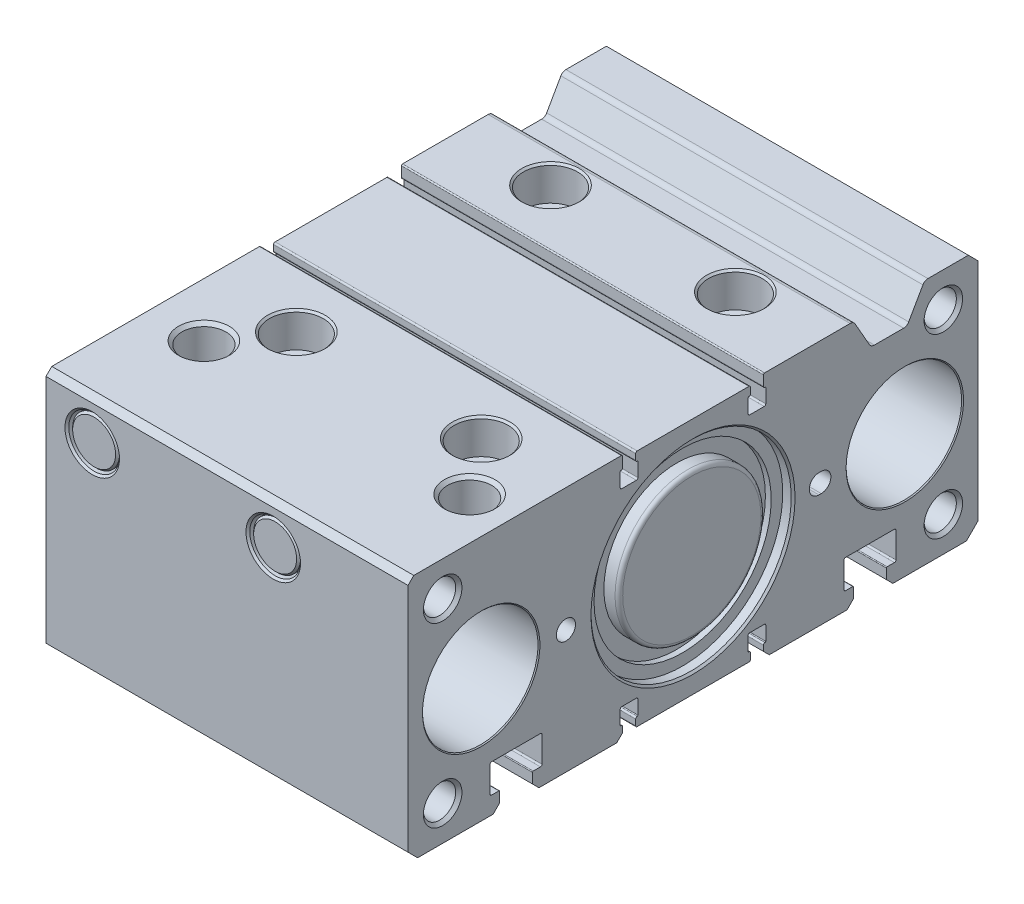
SolidWorks part; units mm, degrees
ref_plane "前视基准面" through (0, 0, 0) normal (0, 0, 1) x (1, 0, 0)
ref_plane "上视基准面" through (0, 0, 0) normal (0, 1, 0) x (1, 0, 0)
ref_plane "右视基准面" through (0, 0, 0) normal (1, 0, 0) x (0, 0, -1)
sketch "草图1" plane through (0, 0, 0) normal (1, 0, 0) x (0, 0, -1)
  line L0 (-74, 30.5) -> (-74, -29.5)
  line L1 (-74, -29.5) -> (-71.5, -32)
  line L2 (-71.5, -32) -> (-51.9, -32)
  line L3 (-51.9, -32) -> (-50.2, -30.3)
  line L4 (-50.2, -30.3) -> (-50.2, -27.7)
  line L5 (-50.4, -27.5) -> (-52.3, -27.5)
  line L6 (-52.7, -27.1) -> (-52.7, -20.4)
  line L7 (-52.3, -20) -> (-39.6, -20)
  line L8 (-39.2, -20.4) -> (-39.2, -27.1)
  line L9 (-39.6, -27.5) -> (-41.5, -27.5)
  line L10 (-41.7, -27.7) -> (-41.7, -30.3)
  line L11 (-41.7, -30.3) -> (-40, -32)
  line L12 (-40, -32) -> (-19.8, -32)
  line L13 (-19.8, -32) -> (-18.3, -30.5)
  line L14 (-18.3, -30.5) -> (-18.3, -29.1)
  line L15 (-18.9, -28.5) -> (-18.9, -24.9)
  line L16 (-18.5, -24.5) -> (-14.7, -24.5)
  line L17 (-14.3, -24.9) -> (-14.3, -28.5)
  line L18 (-14.9, -29.1) -> (-14.9, -30.6)
  line L19 (-14.5, -31) -> (14.5, -31)
  line L20 (14.9, -30.6) -> (14.9, -29.1)
  line L21 (14.3, -28.5) -> (14.3, -24.9)
  line L22 (14.7, -24.5) -> (18.5, -24.5)
  line L23 (18.9, -24.9) -> (18.9, -28.5)
  line L24 (18.3, -29.1) -> (18.3, -30.5)
  line L25 (18.3, -30.5) -> (19.8, -32)
  line L26 (19.8, -32) -> (40, -32)
  line L27 (40, -32) -> (41.7, -30.3)
  line L28 (41.7, -30.3) -> (41.7, -27.7)
  line L29 (41.5, -27.5) -> (39.6, -27.5)
  line L30 (39.2, -27.1) -> (39.2, -20.4)
  line L31 (39.6, -20) -> (52.3, -20)
  line L32 (52.7, -20.4) -> (52.7, -27.1)
  line L33 (52.3, -27.5) -> (50.4, -27.5)
  line L34 (50.2, -27.7) -> (50.2, -30.3)
  line L35 (50.2, -30.3) -> (51.9, -32)
  line L36 (51.9, -32) -> (71, -32)
  line L37 (71, -32) -> (74, -29)
  line L38 (74, -29) -> (74, 29.5)
  line L39 (74, 29.5) -> (71.5, 32)
  line L40 (71.5, 32) -> (61, 32)
  line L41 (59.6966, 31.2423) -> (56.0034, 24.7577)
  line L42 (54.7, 24) -> (47.1, 24)
  line L43 (45.7966, 24.7577) -> (42.1034, 31.2423)
  line L44 (40.8, 32) -> (18.6, 32)
  line L45 (18.3, 31.7) -> (18.3, 29.1)
  line L46 (18.9, 28.5) -> (18.9, 24.9)
  line L47 (18.5, 24.5) -> (14.7, 24.5)
  line L48 (14.3, 24.9) -> (14.3, 28.5)
  line L49 (14.9, 29.1) -> (14.9, 30.6)
  line L50 (14.5, 31) -> (-14.5, 31)
  line L51 (-14.9, 30.6) -> (-14.9, 29.1)
  line L52 (-14.3, 28.5) -> (-14.3, 24.9)
  line L53 (-14.7, 24.5) -> (-18.5, 24.5)
  line L54 (-18.9, 24.9) -> (-18.9, 28.5)
  line L55 (-18.3, 29.1) -> (-18.3, 31.7)
  line L56 (-18.6, 32) -> (-72.5, 32)
  line L57 (-72.5, 32) -> (-74, 30.5)
  arc A0 (-50.2, -27.7) -> (-50.4, -27.5) centre (-50.4, -27.7) ccw
  arc A1 (-52.3, -27.5) -> (-52.7, -27.1) centre (-52.3, -27.1) cw
  arc A2 (-52.7, -20.4) -> (-52.3, -20) centre (-52.3, -20.4) cw
  arc A3 (-39.6, -20) -> (-39.2, -20.4) centre (-39.6, -20.4) cw
  arc A4 (-39.2, -27.1) -> (-39.6, -27.5) centre (-39.6, -27.1) cw
  arc A5 (-41.5, -27.5) -> (-41.7, -27.7) centre (-41.5, -27.7) ccw
  arc A6 (-18.3, -29.1) -> (-18.7, -28.7) centre (-18.7, -29.1) ccw
  arc A7 (-18.7, -28.7) -> (-18.9, -28.5) centre (-18.7, -28.5) cw
  arc A8 (-18.9, -24.9) -> (-18.5, -24.5) centre (-18.5, -24.9) cw
  arc A9 (-14.7, -24.5) -> (-14.3, -24.9) centre (-14.7, -24.9) cw
  arc A10 (-14.3, -28.5) -> (-14.5, -28.7) centre (-14.5, -28.5) cw
  arc A11 (-14.5, -28.7) -> (-14.9, -29.1) centre (-14.5, -29.1) ccw
  arc A12 (-14.9, -30.6) -> (-14.5, -31) centre (-14.5, -30.6) ccw
  arc A13 (14.5, -31) -> (14.9, -30.6) centre (14.5, -30.6) ccw
  arc A14 (14.9, -29.1) -> (14.5, -28.7) centre (14.5, -29.1) ccw
  arc A15 (14.5, -28.7) -> (14.3, -28.5) centre (14.5, -28.5) cw
  arc A16 (14.3, -24.9) -> (14.7, -24.5) centre (14.7, -24.9) cw
  arc A17 (18.5, -24.5) -> (18.9, -24.9) centre (18.5, -24.9) cw
  arc A18 (18.9, -28.5) -> (18.7, -28.7) centre (18.7, -28.5) cw
  arc A19 (18.7, -28.7) -> (18.3, -29.1) centre (18.7, -29.1) ccw
  arc A20 (41.7, -27.7) -> (41.5, -27.5) centre (41.5, -27.7) ccw
  arc A21 (39.6, -27.5) -> (39.2, -27.1) centre (39.6, -27.1) cw
  arc A22 (39.2, -20.4) -> (39.6, -20) centre (39.6, -20.4) cw
  arc A23 (52.3, -20) -> (52.7, -20.4) centre (52.3, -20.4) cw
  arc A24 (52.7, -27.1) -> (52.3, -27.5) centre (52.3, -27.1) cw
  arc A25 (50.4, -27.5) -> (50.2, -27.7) centre (50.4, -27.7) ccw
  arc A26 (61, 32) -> (59.6966, 31.2423) centre (61, 30.5) ccw
  arc A27 (56.0034, 24.7577) -> (54.7, 24) centre (54.7, 25.5) cw
  arc A28 (47.1, 24) -> (45.7966, 24.7577) centre (47.1, 25.5) cw
  arc A29 (42.1034, 31.2423) -> (40.8, 32) centre (40.8, 30.5) ccw
  arc A30 (18.6, 32) -> (18.3, 31.7) centre (18.6, 31.7) ccw
  arc A31 (18.3, 29.1) -> (18.7, 28.7) centre (18.7, 29.1) ccw
  arc A32 (18.7, 28.7) -> (18.9, 28.5) centre (18.7, 28.5) cw
  arc A33 (18.9, 24.9) -> (18.5, 24.5) centre (18.5, 24.9) cw
  arc A34 (14.7, 24.5) -> (14.3, 24.9) centre (14.7, 24.9) cw
  arc A35 (14.3, 28.5) -> (14.5, 28.7) centre (14.5, 28.5) cw
  arc A36 (14.5, 28.7) -> (14.9, 29.1) centre (14.5, 29.1) ccw
  arc A37 (14.9, 30.6) -> (14.5, 31) centre (14.5, 30.6) ccw
  arc A38 (-14.5, 31) -> (-14.9, 30.6) centre (-14.5, 30.6) ccw
  arc A39 (-14.9, 29.1) -> (-14.5, 28.7) centre (-14.5, 29.1) ccw
  arc A40 (-14.5, 28.7) -> (-14.3, 28.5) centre (-14.5, 28.5) cw
  arc A41 (-14.3, 24.9) -> (-14.7, 24.5) centre (-14.7, 24.9) cw
  arc A42 (-18.5, 24.5) -> (-18.9, 24.9) centre (-18.5, 24.9) cw
  arc A43 (-18.9, 28.5) -> (-18.7, 28.7) centre (-18.7, 28.5) cw
  arc A44 (-18.7, 28.7) -> (-18.3, 29.1) centre (-18.7, 29.1) ccw
  arc A45 (-18.3, 31.7) -> (-18.6, 32) centre (-18.6, 31.7) ccw
extrude "凸台-拉伸1" add sketch "草图1" along normal blind 94
ref_plane "基准面1" through (0, 0, 33) normal (0, 0, 1) x (1, 0, 0)
sketch "草图2" plane through (0, 0, 33) normal (0, 0, 1) x (1, 0, 0)
  line L0 (24, 32) -> (31.5, 32)
  line L1 (31.5, 32) -> (31, 31.5)
  line L2 (31, 31.5) -> (31, 23)
  line L3 (31, 23) -> (28.25, 23)
  line L4 (28.25, 23) -> (28.25, -13)
  line L5 (28.25, -13) -> (29, -13)
  line L6 (29, -13) -> (28.188, -13.812)
  line L7 (28.188, -13.812) -> (28.188, -32.188)
  line L8 (28.188, -32.188) -> (29, -33)
  line L9 (29, -33) -> (24, -33)
  line L10 (24, -33) -> (24, 32)
  line L11 (24, -33) -> (24, 32) construction
revolve "切除-旋转1" cut sketch "草图2" angle 360 about L11 reverse direction yes
cosmetic thread "装饰螺纹线1" parameters "D1"=19, "D2"=10
ref_plane "基准面2" through (0, -33, 0) normal (0, 1, 0) x (1, 0, 0)
sketch "草图3" plane through (0, -33, 0) normal (0, 1, 0) x (1, 0, 0)
  line L0 (24, -33) -> (72, -33)
  line L1 (24, -33) -> (24, 33)
pattern_linear "阵列(线性)1" count 2 spacing 48 along (1, 0, 0) count 2 spacing 66 along (0, 0, -1) of "切除-旋转1"
ref_plane "基准面3" through (0, 0, 55) normal (0, 0, 1) x (1, 0, 0)
sketch "草图4" plane through (0, 0, 55) normal (0, 0, 1) x (1, 0, 0)
  line L0 (0, 0) -> (0, 16.25)
  line L1 (0, 16.25) -> (0.25, 16)
  line L2 (0.25, 16) -> (1.5, 16)
  line L3 (1.5, 16) -> (1.5, 10)
  line L4 (1.5, 10) -> (20, 10)
  line L5 (20, 10) -> (20, 15)
  line L6 (20, 15) -> (93.75, 15)
  line L7 (93.75, 15) -> (94, 15.25)
  line L8 (94, 15.25) -> (94, 0)
  line L9 (94, 0) -> (0, 0)
  line L10 (94, 0) -> (0, 0) construction
revolve "切除-旋转2" cut sketch "草图4" angle 360 about L10 reverse direction yes
ref_plane "基准面4" through (0, 0, -55) normal (0, 0, 1) x (1, 0, 0)
sketch "草图5" plane through (0, 0, -55) normal (0, 0, 1) x (1, 0, 0)
  line L0 (0, 0) -> (0, 16.25)
  line L1 (0, 16.25) -> (0.25, 16)
  line L2 (0.25, 16) -> (1.5, 16)
  line L3 (1.5, 16) -> (1.5, 10)
  line L4 (1.5, 10) -> (20, 10)
  line L5 (20, 10) -> (20, 15)
  line L6 (20, 15) -> (93.75, 15)
  line L7 (93.75, 15) -> (94, 15.25)
  line L8 (94, 15.25) -> (94, 0)
  line L9 (94, 0) -> (0, 0)
  line L10 (94, 0) -> (0, 0) construction
revolve "切除-旋转3" cut sketch "草图5" angle 360 about L10 reverse direction yes
sketch "草图6" plane through (0, 0, 0) normal (0, 0, 1) x (1, 0, 0)
  line L0 (0, 0) -> (0, 26.25)
  line L1 (0, 26.25) -> (0.25, 26)
  line L2 (0.25, 26) -> (2.7, 26)
  line L3 (2.7, 26) -> (2.7, 23)
  line L4 (2.7, 23) -> (4.2, 23)
  line L5 (4.2, 23) -> (4.2, 10)
  line L6 (4.2, 10) -> (16.4, 10)
  line L7 (16.4, 10) -> (16.4, 25)
  line L8 (16.4, 25) -> (88, 25)
  line L9 (88, 25) -> (88, 0)
  line L10 (88, 0) -> (0, 0)
  line L11 (88, 0) -> (0, 0) construction
revolve "切除-旋转4" cut sketch "草图6" angle 360 about L11 reverse direction yes
sketch "草图7" plane through (0, 0, 0) normal (0, 0, 1) x (1, 0, 0)
  line L0 (89.8, 0) -> (89.8, 23)
  line L1 (89.8, 23) -> (91.3, 23)
  line L2 (91.3, 23) -> (91.3, 26)
  line L3 (91.3, 26) -> (93.5, 26)
  line L4 (93.5, 26) -> (94, 26.5)
  line L5 (94, 26.5) -> (94, 0)
  line L6 (94, 0) -> (89.8, 0)
  line L7 (94, 0) -> (89.8, 0) construction
revolve "切除-旋转5" cut sketch "草图7" angle 360 about L7 reverse direction yes
sketch "草图8" plane through (0, 0, 0) normal (0, 0, 1) x (1, 0, 0)
  line L0 (89.8, 0) -> (89.8, 18.95)
  line L1 (89.8, 18.95) -> (92.7, 18.95)
  line L2 (93.7, 17.95) -> (93.7, 0)
  line L3 (93.7, 0) -> (89.8, 0)
  line L4 (93.7, 0) -> (89.8, 0) construction
  arc A0 (92.7, 18.95) -> (93.7, 17.95) centre (92.7, 17.95) cw
revolve "旋转1" add sketch "草图8" angle 360 about L4 reverse direction yes
ref_plane "基准面5" through (91.8, 0, 0) normal (1, 0, 0) x (0, 0, -1)
ref_plane "基准面6" through (2.2, 0, 0) normal (1, 0, 0) x (0, 0, -1)
sketch "草图9" plane through (0, 0, 0) normal (0, 0, 1) x (1, 0, 0)
  line L0 (0.3, 10) -> (5.3, 10)
  line L1 (5.3, 10) -> (5.3, 18.95)
  line L2 (5.3, 18.95) -> (1.05, 18.95)
  line L3 (0.3, 18.2) -> (0.3, 10)
  line L4 (5.3, 0) -> (0.3, 0) construction
  arc A0 (1.05, 18.95) -> (0.3, 18.2) centre (1.05, 18.2) ccw
revolve "旋转2" add sketch "草图9" angle 360 about L4 reverse direction yes
ref_plane "基准面7" through (0, 0, 47) normal (0, 0, 1) x (1, 0, 0)
hole_wizard "孔1" positions "草图11" profile "草图10" legacy
sketch "草图11" plane through (0, 32, 0) normal (0, 1, 0) x (1, 0, 0)
  point P0 (14, -47)
sketch "草图10" plane through (14, 32, 47) normal (1, 0, 0) x (0, 0, 1)
  line L0 (0, 0) -> (0, 13.05)
  line L1 (0, 13.05) -> (5.7225, 13.05)
  line L2 (5.7225, 13.05) -> (5.7225, 0.856)
  line L3 (5.7225, 0.856) -> (6.5785, 0)
  line L4 (6.5785, 0) -> (0, 0)
  line L5 (0, -6.4453) -> (0, 115.525) construction
  line L6 (-5.7225, 0.856) -> (-6.5785, 0) construction
  dimension "直径" = 11.445
  dimension "深度" = 13.05
  dimension "锥坑角度" = 90
  dimension "锥坑直径" = 13.157
cosmetic thread "装饰螺纹线2" parameters "D1"=12, "D2"=13.157
hole_wizard "孔2" positions "草图13" profile "草图12" legacy
sketch "草图13" plane through (0, 32, 0) normal (0, 1, 0) x (1, 0, 0)
  point P0 (83, -47)
sketch "草图12" plane through (83, 32, 47) normal (1, 0, 0) x (0, 0, 1)
  line L0 (0, 0) -> (0, 13.05)
  line L1 (0, 13.05) -> (5.7225, 13.05)
  line L2 (5.7225, 13.05) -> (5.7225, 0.856)
  line L3 (5.7225, 0.856) -> (6.5785, 0)
  line L4 (6.5785, 0) -> (0, 0)
  line L5 (0, -6.4453) -> (0, 115.525) construction
  line L6 (-5.7225, 0.856) -> (-6.5785, 0) construction
  dimension "直径" = 11.445
  dimension "深度" = 13.05
  dimension "锥坑角度" = 90
  dimension "锥坑直径" = 13.157
cosmetic thread "装饰螺纹线3" parameters "D1"=12, "D2"=13.157
ref_plane "基准面8" through (12, 0, 0) normal (1, 0, 0) x (0, 0, -1)
sketch "草图14" plane through (12, 0, 0) normal (1, 0, 0) x (0, 0, -1)
  line L0 (-74, 21.5) -> (-74, 28.5785)
  line L1 (-74, 28.5785) -> (-73.5, 28.0785)
  line L2 (-73.5, 28.0785) -> (-69.5, 28.0785)
  line L3 (-69.5, 28.0785) -> (-69.5, 27.5785)
  line L4 (-69.5, 27.5785) -> (-73, 27.5785)
  line L5 (-73, 27.5785) -> (-73.5, 27.0785)
  line L6 (-73.5, 27.0785) -> (-73.5, 21.5)
  line L7 (-73.5, 21.5) -> (-74, 21.5)
  line L8 (-69.5, 21.5) -> (-74, 21.5) construction
revolve "切除-旋转6" cut sketch "草图14" angle 360 about L8 reverse direction yes
ref_plane "基准面9" through (59, 0, 0) normal (1, 0, 0) x (0, 0, -1)
sketch "草图15" plane through (59, 0, 0) normal (1, 0, 0) x (0, 0, -1)
  line L0 (-74, 21.5) -> (-74, 28.5785)
  line L1 (-74, 28.5785) -> (-73.5, 28.0785)
  line L2 (-73.5, 28.0785) -> (-69.5, 28.0785)
  line L3 (-69.5, 28.0785) -> (-69.5, 27.5785)
  line L4 (-69.5, 27.5785) -> (-73, 27.5785)
  line L5 (-73, 27.5785) -> (-73.5, 27.0785)
  line L6 (-73.5, 27.0785) -> (-73.5, 21.5)
  line L7 (-73.5, 21.5) -> (-74, 21.5)
  line L8 (-69.5, 21.5) -> (-74, 21.5) construction
revolve "切除-旋转7" cut sketch "草图15" angle 360 about L8 reverse direction yes
ref_plane "基准面10" through (83, 0, 0) normal (1, 0, 0) x (0, 0, -1)
ref_plane "基准面11" through (0, 0, 33) normal (0, 0, 1) x (1, 0, 0)
sketch "草图16" plane through (0, 0, 33) normal (0, 0, 1) x (1, 0, 0)
  line L0 (48, -25) -> (50.5, -25)
  line L1 (50.5, -25) -> (50.5, -33)
  line L2 (50.5, -33) -> (48, -33)
  line L3 (48, -33) -> (48, -25)
  line L4 (48, -33) -> (48, -25) construction
revolve "切除-旋转8" cut sketch "草图16" angle 360 about L4 reverse direction yes
ref_plane "基准面12" through (0, 0, -33) normal (0, 0, 1) x (1, 0, 0)
sketch "草图17" plane through (0, 0, -33) normal (0, 0, 1) x (1, 0, 0)
  line L0 (48, -23.5566) -> (50.5, -25)
  line L1 (50.5, -25) -> (50.5, -33)
  line L2 (50.5, -33) -> (48, -33)
  line L3 (48, -33) -> (48, -23.5566)
  line L4 (48, -33) -> (48, -23.5566) construction
revolve "切除-旋转9" cut sketch "草图17" angle 360 about L4 reverse direction yes
ref_plane "基准面13" through (0, 0, 65) normal (0, 0, 1) x (1, 0, 0)
hole_wizard "孔3" positions "草图19" profile "草图18" legacy
sketch "草图19" plane through (94, 0, 0) normal (1, 0, 0) x (0, 0, -1)
  point P0 (-65, -23)
sketch "草图18" plane through (94, -23, 65) normal (0, 1, 0) x (0, 0, -1)
  line L0 (0, 0) -> (0, 28.8179)
  line L1 (0, 28.8179) -> (4.188, 26.4)
  line L2 (4.188, 26.4) -> (4.188, 0.812)
  line L3 (4.188, 0.812) -> (5, 0)
  line L4 (5, 0) -> (0, 0)
  line L5 (0, -14.3089) -> (0, 102.4216) construction
  line L6 (0, 28.8179) -> (-4.188, 26.4) construction
  line L7 (-4.188, 0.812) -> (-5, 0) construction
  dimension "直径" = 8.376
  dimension "深度" = 26.4
  dimension "锥坑直径" = 10
  dimension "锥坑角度" = 90
  dimension "导头角度" = 120
cosmetic thread "装饰螺纹线4" parameters "D1"=22, "D2"=10
ref_plane "基准面14" through (94, 0, 0) normal (1, 0, 0) x (0, 0, -1)
sketch "草图20" plane through (94, 0, 0) normal (1, 0, 0) x (0, 0, -1)
  line L0 (-65, -23) -> (65, -23)
  line L1 (-65, -23) -> (-65, 23)
pattern_linear "阵列(线性)2" count 2 spacing 130 along (0, 0, -1) count 2 spacing 46 along (0, 1, 0) of "孔3"
hole_wizard "孔4" positions "草图22" profile "草图21" legacy
sketch "草图22" plane through (94, 0, 0) normal (1, 0, 0) x (0, 0, -1)
  point P0 (-33, 0)
sketch "草图21" plane through (94, 0, 33) normal (0, 1, 0) x (0, 0, -1)
  line L0 (0, 0) -> (0, 8)
  line L1 (0, 8) -> (2.5, 8)
  line L2 (2.5, 8) -> (2.5, 0)
  line L3 (2.5, 0) -> (0, 0)
  line L4 (0, 110) -> (0, -10) construction
  dimension "直径" = 5
  dimension "深度" = 8
hole_wizard "孔5" positions "草图24" profile "草图23" legacy
sketch "草图24" plane through (94, 0, 0) normal (1, 0, 0) x (0, 0, -1)
  point P0 (33, 0)
sketch "草图23" plane through (94, 0, -33) normal (0, 1, 0) x (0, 0, -1)
  line L0 (0, 0) -> (0, 9.4434)
  line L1 (0, 9.4434) -> (2.5, 8)
  line L2 (2.5, 8) -> (2.5, 0)
  line L4 (2.5, 0) -> (0, 0)
  line L6 (0, 9.4434) -> (-2.5, 8) construction
  line L7 (0, -4.2442) -> (0, 117.3081) construction
  dimension "直径" = 5
  dimension "深度" = 8
  dimension "导头角度" = 120
ref_plane "基准面15" through (0, -32, 0) normal (0, 1, 0) x (1, 0, 0)
sketch "草图25" plane through (0, -32, 0) normal (0, 1, 0) x (1, 0, 0)
  line L0 (50.5, 32.7) -> (50.5, 33.3)
  line L1 (45.5, 33.3) -> (45.5, 32.7)
  arc A0 (45.5, 32.7) -> (50.5, 32.7) centre (48, 32.7) ccw
  arc A1 (50.5, 33.3) -> (45.5, 33.3) centre (48, 33.3) ccw
extrude "切除-拉伸1" cut sketch "草图25" along normal blind 4
ref_plane "基准面16" through (94, 0, 0) normal (1, 0, 0) x (0, 0, -1)
sketch "草图26" plane through (94, 0, 0) normal (1, 0, 0) x (0, 0, -1)
  line L0 (32.7, -2.5) -> (33.3, -2.5)
  line L1 (33.3, 2.5) -> (32.7, 2.5)
  arc A0 (32.7, 2.5) -> (32.7, -2.5) centre (32.7, 0) ccw
  arc A1 (33.3, -2.5) -> (33.3, 2.5) centre (33.3, 0) ccw
extrude "切除-拉伸2" cut sketch "草图26" against normal blind 4
ref_plane "基准面17" through (-28, 0, 0) normal (1, 0, 0) x (0, 0, -1)
ref_plane "基准面18" through (1, 0, 0) normal (1, 0, 0) x (0, 0, -1)
ref_plane "基准面19" through (93, 0, 0) normal (1, 0, 0) x (0, 0, -1)
ref_plane "IP_SWITCH1 XY" through (1, 0, 0) normal (-1, 0, 0) x (0, 0, 1)
ref_plane "IP_SWITCH1 XZ" through (0, 24.5, 0) normal (0, 1, 0) x (1, 0, 0)
ref_plane "IP_SWITCH1 YZ" through (0, 0, -16.6) normal (0, 0, -1) x (-1, 0, 0)
ref_axis "IP_SWITCH1 X" through (1, 24.5, 80.9) along (0, 0, -1)
ref_axis "IP_SWITCH1 Y" through (1, 50, -16.6) along (0, -1, 0)
ref_axis "IP_SWITCH1 Z" through (-80.9, 24.5, -16.6) along (1, 0, 0)
sketch3d "IP_SWITCH1"
  point P0 (1, 24.5, -16.6)
ref_plane "IP_SWITCH2 XY" through (93, 0, 0) normal (1, 0, 0) x (0, 0, -1)
ref_plane "IP_SWITCH2 XZ" through (0, -24.5, 0) normal (0, -1, 0) x (-1, 0, 0)
ref_plane "IP_SWITCH2 YZ" through (0, 0, 16.6) normal (0, 0, -1) x (-1, 0, 0)
ref_axis "IP_SWITCH2 X" through (93, -24.5, 80.9) along (0, 0, -1)
ref_axis "IP_SWITCH2 Y" through (93, -50, 16.6) along (0, 1, 0)
ref_axis "IP_SWITCH2 Z" through (80.9, -24.5, 16.6) along (-1, 0, 0)
sketch3d "IP_SWITCH2"
  point P0 (93, -24.5, 16.6)
ref_plane "for_dummy XY" through (0, 0, 0) normal (1, 0, 0) x (0, 0, -1)
ref_plane "for_dummy XZ" through (0, 0, 0) normal (0, -1, 0) x (-1, 0, 0)
ref_plane "for_dummy YZ" through (0, 0, 0) normal (0, 0, -1) x (-1, 0, 0)
ref_axis "for_dummy X" through (0, 0, 80.9) along (0, 0, -1)
ref_axis "for_dummy Y" through (0, -50, 0) along (0, 1, 0)
ref_axis "for_dummy Z" through (80.9, 0, 0) along (-1, 0, 0)
sketch3d "for_dummy"
  point P0 (0, 0, 0)
ref_plane "for_rod XY" through (-28, 0, 0) normal (-1, 0, 0) x (0, 0, 1)
ref_plane "for_rod XZ" through (0, 0, 0) normal (0, 1, 0) x (1, 0, 0)
ref_plane "for_rod YZ" through (0, 0, 0) normal (0, 0, -1) x (-1, 0, 0)
ref_axis "for_rod X" through (-28, 0, 80.9) along (0, 0, -1)
ref_axis "for_rod Y" through (-28, 50, 0) along (0, -1, 0)
ref_axis "for_rod Z" through (-80.9, 0, 0) along (1, 0, 0)
sketch3d "for_rod"
  point P0 (-28, 0, 0)
